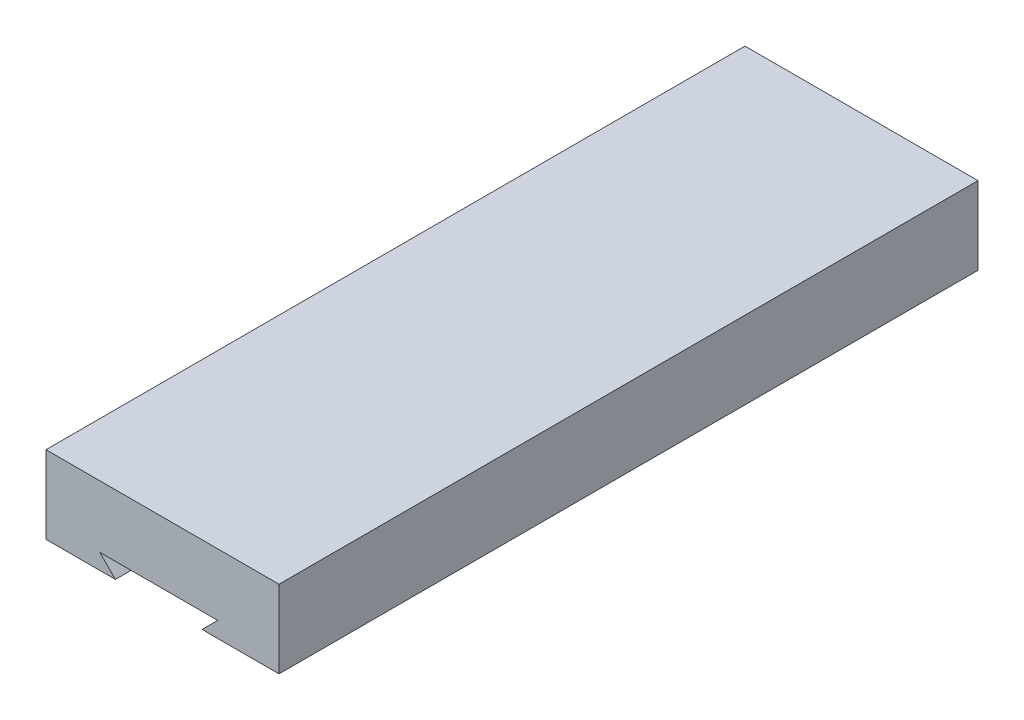
SolidWorks part; units mm, degrees
ref_plane "Front Plane" through (0, 0, 0) normal (0, 0, 1) x (1, 0, 0)
ref_plane "Top Plane" through (0, 0, 0) normal (0, 1, 0) x (1, 0, 0)
ref_plane "Right Plane" through (0, 0, 0) normal (1, 0, 0) x (0, 0, -1)
sketch "Sketch1" plane through (0, 0, 0) normal (0, 0, 1) x (1, 0, 0)
  line L1 (-31.0211, 23.825) -> (28.9789, 23.825)
  line L2 (-31.0211, 23.825) -> (-31.0211, 3.825)
  line L3 (-31.0211, 3.825) -> (28.9789, 3.825)
  line L4 (28.9789, 23.825) -> (28.9789, 3.825)
  dimension "D1" = 60
  dimension "D2" = 20
extrude "Boss-Extrude1" add sketch "Sketch1" along normal blind 180
sketch "Sketch2" plane through (0, 0, 180) normal (0, 0, 1) x (1, 0, 0)
  line L0 (-13.1448, 3.825) -> (-17.1805, 7.8607)
  line L1 (-31.0211, 3.825) -> (28.9789, 3.825) construction
  line L2 (-17.1805, 7.8607) -> (13.1879, 7.8607)
  line L3 (13.1879, 7.8607) -> (9.1521, 3.825)
  line L4 (-13.1448, 3.825) -> (9.1521, 3.825)
  dimension "D1" = 45
  dimension "D2" = 45
extrude "Cut-Extrude1" cut sketch "Sketch2" against normal blind 180 and the other way through all
